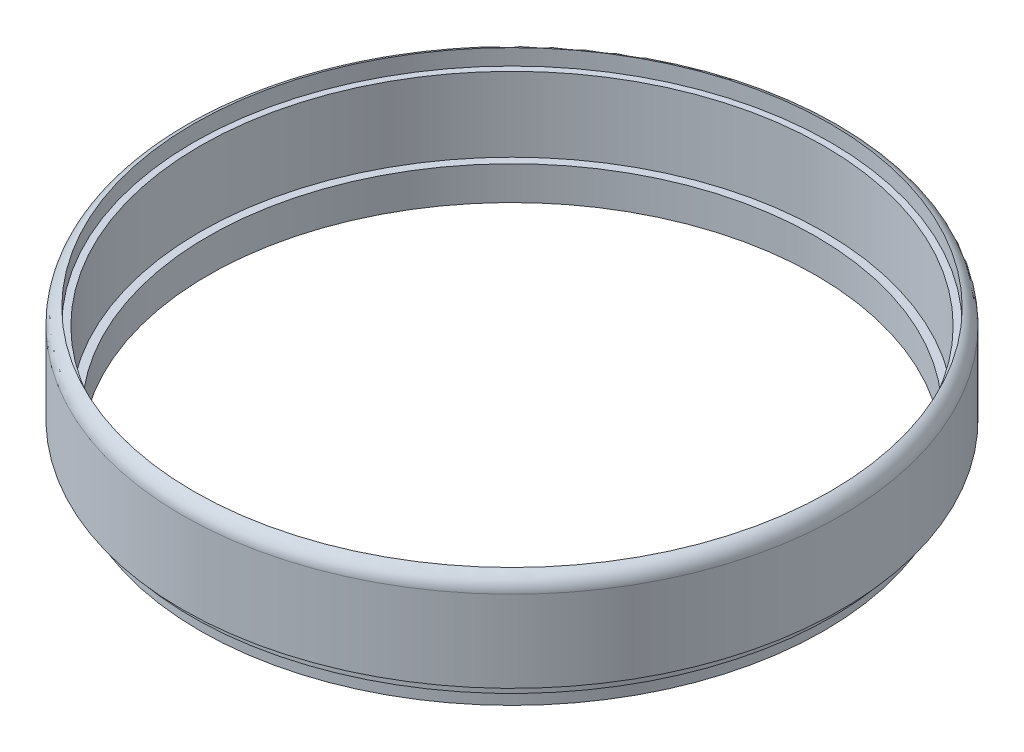
SolidWorks part; units mm, degrees
material "Alliage 1060"
ref_plane "Plan de face" through (0, 0, 0) normal (0, 0, 1) x (1, 0, 0)
ref_plane "Plan de dessus" through (0, 0, 0) normal (0, 1, 0) x (1, 0, 0)
ref_plane "Plan de droite" through (0, 0, 0) normal (1, 0, 0) x (0, 0, -1)
sketch "Esquisse1" plane through (0, 0, 0) normal (0, 0, 1) x (1, 0, 0)
  line L0 (19, 2.1) -> (19, 0)
  line L1 (19, 0) -> (19.5, 0)
  line L2 (19.5, 0) -> (19.5, 1)
  line L3 (19.5, 1) -> (20, 1)
  line L4 (20, 1) -> (20, 1.7)
  line L7 (19.9, 7.75) -> (20.6, 7.75)
  line L8 (20.6, 7.75) -> (20.6, 1.7)
  line L9 (19.5, 2.1) -> (19, 2.1)
  line L10 (0, 0) -> (0, 11.6202) construction
  line L11 (19.5, 2.1) -> (19.5, 6.75)
  line L13 (0, 0) -> (19, 0) construction
  line L14 (20, 1.7) -> (20.6, 1.7)
  line L15 (19.9, 7.75) -> (19.9, 6.75)
  line L16 (19.9, 6.75) -> (19.5, 6.75)
  dimension "D1" = 0.5
  dimension "D2" = 7.75
  dimension "D3" = 0.5
  dimension "D4" = 0.7
  dimension "D5" = 19.5
  dimension "D6" = 41.2
  dimension "D7" = 1
  dimension "D8" = 1
  dimension "D9" = 0.4
  dimension "D10" = 2.1
  dimension "D11" = 39
revolve "Révolution1" add sketch "Esquisse1" angle 360 about L10
fillet "Congé1" radius 1 1 edges at (0, 7.75, -20.6)
